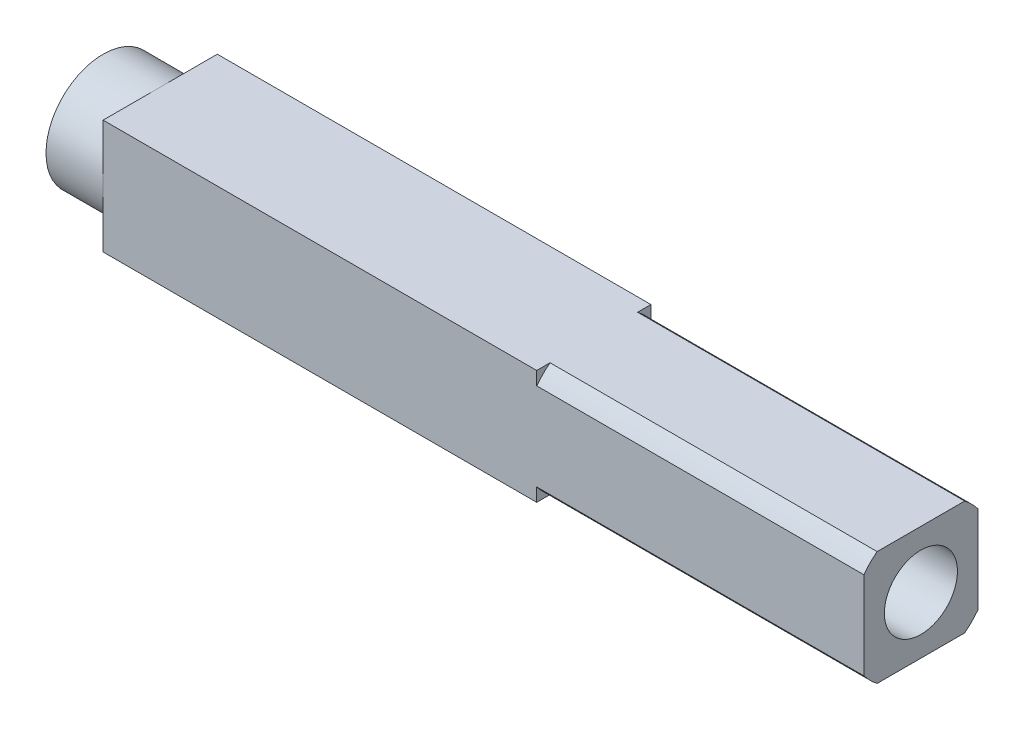
SolidWorks part; units mm, degrees
ref_plane "Front Plane" through (0, 0, 0) normal (0, 0, 1) x (1, 0, 0)
ref_plane "Top Plane" through (0, 0, 0) normal (0, 1, 0) x (1, 0, 0)
ref_plane "Right Plane" through (0, 0, 0) normal (1, 0, 0) x (0, 0, -1)
sketch "Sketch1" plane through (0, 0, 0) normal (1, 0, 0) x (0, 0, -1)
  line L1 (-3.175, -3.175) -> (3.175, -3.175)
  line L2 (-3.175, -3.175) -> (-3.175, 3.175)
  line L3 (-3.175, 3.175) -> (3.175, 3.175)
  line L4 (3.175, -3.175) -> (3.175, 3.175)
  line L5 (-3.175, -3.175) -> (3.175, 3.175) construction
  line L6 (-3.175, 3.175) -> (3.175, -3.175) construction
  point P0 (0, 0)
  dimension "D1" = 6.35
extrude "Boss-Extrude1" add sketch "Sketch1" along normal blind 27.2821
sketch "Sketch3" plane through (0, 0, 0) normal (-1, 0, 0) x (0, 0, 1)
  line L1 (-3.175, 3.175) -> (3.175, 3.175) construction
  line L3 (4.7625, -4.7625) -> (-4.7625, -4.7625)
  line L4 (4.7625, -4.7625) -> (4.7625, 4.7625)
  line L5 (4.7625, 4.7625) -> (-4.7625, 4.7625)
  line L6 (-4.7625, -4.7625) -> (-4.7625, 4.7625)
  line L7 (4.7625, -4.7625) -> (-4.7625, 4.7625) construction
  line L8 (4.7625, 4.7625) -> (-4.7625, -4.7625) construction
  circle A0 centre (0, 0) radius 3.175
  point P2 (0, 0)
  dimension "D1" = 9.525
extrude "Cut-Extrude2" cut sketch "Sketch3" against normal blind 3.175
sketch "Sketch4" plane through (27.2821, 0, 0) normal (1, 0, 0) x (0, 0, -1)
  line L4 (3.175, -3.175) -> (3.175, 3.175)
  line L5 (3.175, 3.175) -> (-3.175, 3.175)
  line L6 (-3.175, 3.175) -> (-3.175, -3.175)
  line L7 (-3.175, -3.175) -> (3.175, -3.175)
  line L8 (3.175, -2.433) -> (3.175, 2.433)
  line L9 (2.433, 3.175) -> (-2.433, 3.175)
  line L10 (-3.175, 2.433) -> (-3.175, -2.433)
  line L11 (-2.433, -3.175) -> (2.433, -3.175)
  arc A0 (-3.175, -2.433) -> (-2.433, -3.175) centre (0, 0) ccw
  arc A1 (2.433, -3.175) -> (3.175, -2.433) centre (0, 0) ccw
  arc A2 (3.175, 2.433) -> (2.433, 3.175) centre (0, 0) ccw
  arc A3 (-2.433, 3.175) -> (-3.175, 2.433) centre (0, 0) ccw
  dimension "D1" = 8
  dimension "D2" = 0
extrude "Boss-Extrude2" add sketch "Sketch4" along normal blind 18.1839
sketch "Sketch5" plane through (45.466, 0, 0) normal (1, 0, 0) x (0, 0, -1)
  circle A0 centre (0, 0) radius 2.032
  dimension "D1" = 4.064
extrude "Cut-Extrude3" cut sketch "Sketch5" against normal blind 25.4
